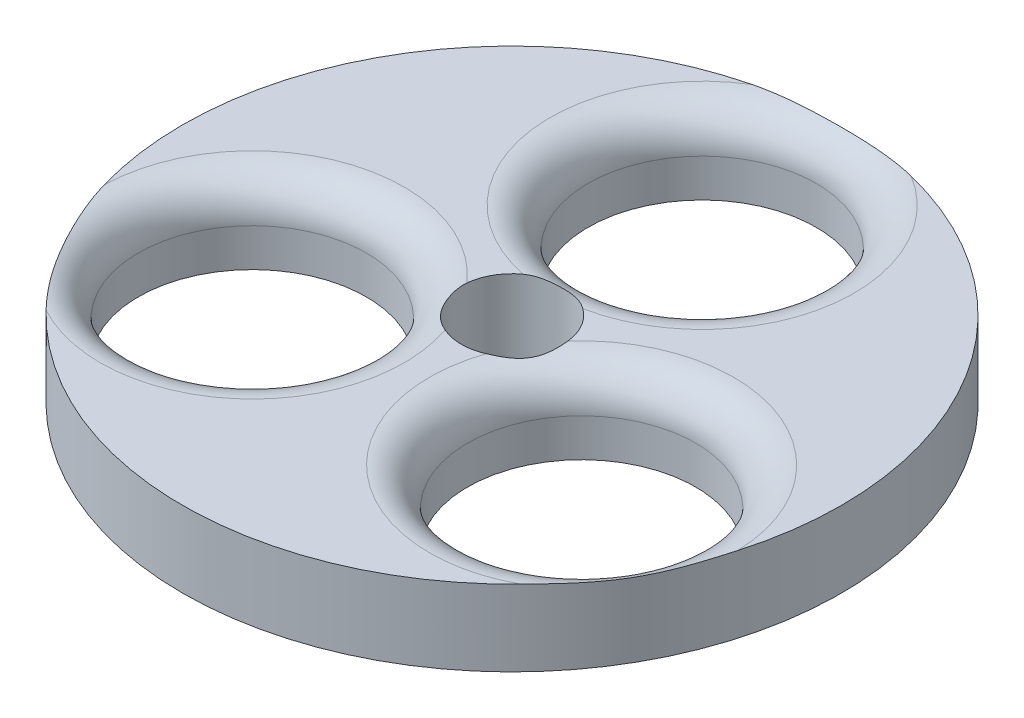
SolidWorks part; units mm, degrees
ref_plane "Front Plane" through (0, 0, 0) normal (0, 0, 1) x (1, 0, 0)
ref_plane "Top Plane" through (0, 0, 0) normal (0, 1, 0) x (1, 0, 0)
ref_plane "Right Plane" through (0, 0, 0) normal (1, 0, 0) x (0, 0, -1)
sketch "Sketch2" plane through (0, 0, 0) normal (0, 1, 0) x (1, 0, 0)
  circle A0 centre (0, 0) radius 130
  circle A1 centre (0, 75) radius 45
  circle A2 centre (64.9519, -37.5) radius 45
  circle A3 centre (-64.9519, -37.5) radius 45
  circle A4 centre (0, 0) radius 20
  point P12 (0, 0)
  dimension "D1" = 260
  dimension "D2" = 75
  dimension "D3" = 90
  dimension "D5" = 40
  dimension "D4" = 3
extrude "Boss-Extrude2" add sketch "Sketch2" along normal blind 30
fillet "Fillet1" radius 15 3 edges at (64.9519, 30, 82.5) (0, 30, -30) (-64.9519, 30, 82.5)
scale "Scale1" scale about centroid uniform scaling yes scale factor 1.12
